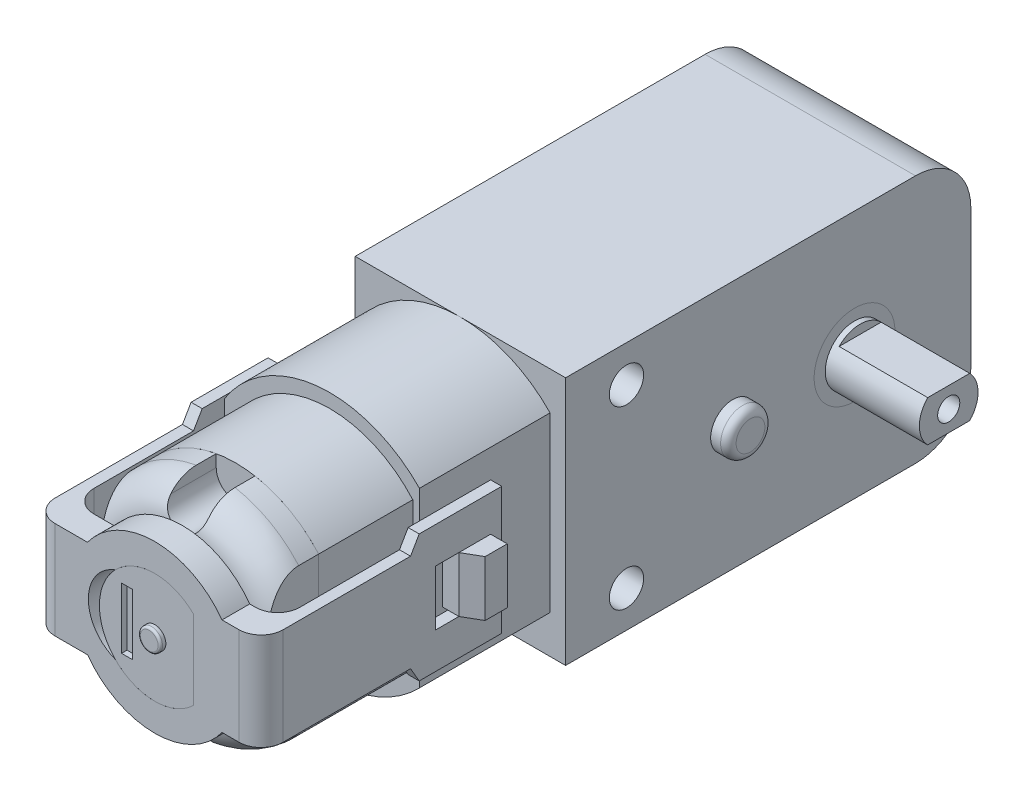
SolidWorks part; units mm, degrees
ref_plane "Alzado" through (0, 0, 0) normal (0, 0, 1) x (1, 0, 0)
ref_plane "Planta" through (0, 0, 0) normal (0, 1, 0) x (1, 0, 0)
ref_plane "Vista lateral" through (0, 0, 0) normal (1, 0, 0) x (0, 0, -1)
sketch "Croquis1" plane through (0, 0, 0) normal (1, 0, 0) x (0, 0, -1)
  line L1 (-18.3, 11.25) -> (13.3, 11.25)
  line L2 (-18.3, 11.25) -> (-18.3, -11.25)
  line L3 (-18.3, -11.25) -> (13.3, -11.25)
  line L4 (18.3, 6.25) -> (18.3, -6.25)
  line L5 (-18.3, 11.25) -> (18.3, -11.25) construction
  line L6 (-18.3, -11.25) -> (18.3, 11.25) construction
  arc A0 (13.3, -11.25) -> (18.3, -6.25) centre (13.3, -6.25) ccw
  arc A1 (13.3, 11.25) -> (18.3, 6.25) centre (13.3, 6.25) cw
  point P0 (0, 0)
  dimension "D3" = 5
  dimension "D1" = 36.6
  dimension "D2" = 22.5
extrude "Saliente-Extruir1" add sketch "Croquis1" along normal mid plane 19
sketch "Croquis2" plane through (9.5, 0, 0) normal (1, 0, 0) x (0, 0, -1)
  line L0 (18.3, 0) -> (-18.3, 0) construction
  line L1 (-18.3, 11.25) -> (-18.3, -11.25) construction
  line L2 (13.3, 11.25) -> (-18.3, 11.25) construction
  circle A0 centre (-12.8, 7.95) radius 1.55
  circle A1 centre (-12.8, -7.95) radius 1.55
  point P6 (0, 0)
  dimension "D1" = 3.1
  dimension "D2" = 3.3
  dimension "D3" = 5.5
extrude "Cortar-Extruir1" cut sketch "Croquis2" against normal through all
sketch "Croquis3" plane through (0, 0, 0) normal (1, 0, 0) x (0, 0, -1)
  line L0 (18.3, -6.25) -> (18.3, 6.25) construction
  line L1 (18.3, 2.5) -> (23.3, 2.5)
  line L2 (18.3, 2.5) -> (18.3, -2.5)
  line L3 (18.3, -2.5) -> (23.3, -2.5)
  line L4 (23.3, 2.5) -> (23.3, -2.5)
  circle A0 centre (20.8, 0) radius 1.55
  point P6 (18.3, 0)
  point P11 (23.3, 0)
  point P13 (20.8, 2.5)
  dimension "D3" = 3.1
  dimension "D1" = 5
  dimension "D2" = 5
extrude "Saliente-Extruir2" add sketch "Croquis3" along normal mid plane 3
sketch "Croquis4" plane through (0, 0, 18.3) normal (0, 0, 1) x (1, 0, 0)
  circle A0 centre (0, 0) radius 11.25
  dimension "D1" = 22.5
extrude "Saliente-Extruir3" add sketch "Croquis4" along normal blind 11.8
sketch "Croquis6" plane through (0, 0, 30.1) normal (0, 0, 1) x (1, 0, 0)
  circle A0 centre (0, 0) radius 10
  dimension "D1" = 20
extrude "Saliente-Extruir4" add sketch "Croquis6" along normal blind 8.5 separate body
sketch "Croquis7" plane through (0, 0, 0) normal (1, 0, 0) x (0, 0, -1)
  line L0 (-38.6, 10) -> (-40.4, 10)
  line L1 (-43.4, 7) -> (-43.4, 5)
  line L3 (-38.6, 10) -> (-38.6, -10) construction
  line L4 (-38.6, 0) -> (-38.6, 10)
  line L5 (18.3, -6.25) -> (18.3, 6.25) construction
  line L6 (-43.4, 5) -> (-45.9, 5)
  line L7 (-45.9, 5) -> (-45.9, 0)
  line L8 (-38.6, 0) -> (-45.9, 0) construction
  line L9 (-38.6, 0) -> (-45.9, 0)
  arc A0 (-40.4, 10) -> (-43.4, 7) centre (-40.4, 7) ccw
  dimension "D1" = 3
  dimension "D2" = 61.7
  dimension "D3" = 2.5
  dimension "D4" = 10
revolve "Revolución1" add sketch "Croquis7" angle 360 about L8
sketch "Croquis8" plane through (0, 0, 30.1) normal (0, 0, 1) x (1, 0, 0)
  line L0 (9.5, -11.25) -> (0, -11.25) construction
  line L1 (-9.5, 11.25) -> (8.1, 11.25)
  line L2 (-9.5, 11.25) -> (-9.5, -11.25)
  line L3 (-9.5, -11.25) -> (8.1, -11.25)
  line L4 (8.1, 11.25) -> (8.1, -11.25)
  line L5 (9.5, -6.026) -> (9.5, -11.25) construction
  line L7 (-13.3448, 14.957) -> (13.3448, 14.957)
  line L8 (-13.3448, 14.957) -> (-13.3448, -14.957)
  line L9 (-13.3448, -14.957) -> (13.3448, -14.957)
  line L10 (13.3448, 14.957) -> (13.3448, -14.957)
  line L11 (-13.3448, 14.957) -> (13.3448, -14.957) construction
  line L12 (-13.3448, -14.957) -> (13.3448, 14.957) construction
  point P9 (0, 0)
  dimension "D1" = 1.4
extrude "Cortar-Extruir2" cut sketch "Croquis8" against normal up to surface (11.8 mm away) up to face at (6.5569, 9.9153, 18.3)
sketch "Croquis9" plane through (0, 0, 45.9) normal (0, 0, 1) x (1, 0, 0)
  line L0 (9.5, -11.25) -> (0, -11.25) construction
  line L1 (-7.5, 11.25) -> (7.5, 11.25)
  line L2 (-7.5, 11.25) -> (-7.5, -11.25)
  line L3 (-7.5, -11.25) -> (7.5, -11.25)
  line L4 (7.5, 11.25) -> (7.5, -11.25)
  line L5 (-7.5, 11.25) -> (7.5, -11.25) construction
  line L6 (-7.5, -11.25) -> (7.5, 11.25) construction
  line L8 (-11.6956, 13.9477) -> (11.6956, 13.9477)
  line L9 (-11.6956, 13.9477) -> (-11.6956, -13.9477)
  line L10 (-11.6956, -13.9477) -> (11.6956, -13.9477)
  line L11 (11.6956, 13.9477) -> (11.6956, -13.9477)
  line L12 (-11.6956, 13.9477) -> (11.6956, -13.9477) construction
  line L13 (-11.6956, -13.9477) -> (11.6956, 13.9477) construction
  point P0 (0, 0)
  point P8 (0, 0)
  dimension "D1" = 15
extrude "Cortar-Extruir3" cut sketch "Croquis9" against normal up to surface (15.8 mm away) up to face at (-0.9164, 0, 30.1)
sketch "Croquis10" plane through (0, 0, 45.9) normal (0, 0, 1) x (1, 0, 0)
  line L1 (3.5, 3.5707) -> (3.5, -3.5707)
  line L2 (-10.6174, 0) -> (10.6174, 0) construction
  circle A1 centre (0, 0) radius 5 construction
  arc A2 (3.5, 3.5707) -> (3.5, -3.5707) centre (0, 0) ccw
  circle A3 centre (0, 0) radius 10.6174
  dimension "D1" = 3.5
extrude "Cortar-Extruir4" cut sketch "Croquis10" against normal up to surface (2.5 mm away) up to face at (0, 5, 43.4)
sketch "Croquis11" plane through (9.5, 0, 0) normal (1, 0, 0) x (0, 0, -1)
  line L0 (18.3, -6.25) -> (18.3, 6.25) construction
  circle A0 centre (7.8, 0) radius 2.65
  circle A1 centre (7.8, 0) radius 3.65
  dimension "D1" = 5.3
  dimension "D3" = 7.3
  dimension "D2" = 10.5
split line "Línea de partición1"
sketch "Croquis12" plane through (9.5, 0, 0) normal (1, 0, 0) x (0, 0, -1)
  circle A1 centre (7.8, 0) radius 2.65
  circle A2 centre (7.8, 0) radius 2.65
  dimension "D1" = 0
extrude "Saliente-Extruir5" add sketch "Croquis12" along normal blind 0.5 separate body
sketch "Croquis13" plane through (10, 0, 0) normal (1, 0, 0) x (0, 0, -1)
  line L0 (5.9026, 1.85) -> (9.6974, 1.85)
  line L1 (5.9026, -1.85) -> (9.6974, -1.85)
  circle A1 centre (7.8, 0) radius 2.65
  circle A2 centre (7.8, 0) radius 2.65
  circle M4 centre (7.8, 0) radius 2.65
  dimension "D2" = 3.7
  dimension "D1" = 0
extrude "Saliente-Extruir6" add sketch "Croquis13" along normal blind 8 contours L1 L0 M4 region at (10, 0, -7.8)
sketch "Croquis14" plane through (18, 0, 0) normal (1, 0, 0) x (0, 0, -1)
  line L0 (5.9026, 1.85) -> (9.6974, 1.85) construction
  circle A0 centre (7.8, 0) radius 1
  arc A1 (9.6974, -1.85) -> (9.6974, 1.85) centre (7.8, 0) ccw construction
  point P5 (7.8, 1.85)
  point P10 (10.45, 0)
  dimension "D1" = 2
extrude "Cortar-Extruir5" cut sketch "Croquis14" against normal blind 8
sketch "Croquis16" plane through (0, 0, 0) normal (0, 1, 0) x (1, 0, 0)
  line L0 (-9.5, -18.3) -> (8.1, -18.3) construction
  line L1 (-0.7, -18.3) -> (-0.7, -30.1) construction
  line L2 (7.5, -30.1) -> (-7.5, -30.1) construction
  line L4 (8.1, -18.3) -> (8.1, -30.1) construction
  line L5 (9.6, -26.5336) -> (9.6, -25.1676)
  line L6 (9.6, -25.1676) -> (11.1, -25.1676)
  line L7 (11.1, -25.1676) -> (11.1, -27.1676)
  line L8 (11.1, -27.1676) -> (8.1, -28.8996)
  line L9 (8.1, -28.8996) -> (8.1, -27.3996)
  line L10 (9.6, -26.5336) -> (8.1, -27.3996)
  line L11 (-11, -26.5336) -> (-9.5, -27.3996)
  line L12 (-9.5, -28.8996) -> (-9.5, -27.3996)
  line L13 (-12.5, -27.1676) -> (-9.5, -28.8996)
  line L14 (-12.5, -25.1676) -> (-12.5, -27.1676)
  line L15 (-11, -25.1676) -> (-12.5, -25.1676)
  line L16 (-11, -26.5336) -> (-11, -25.1676)
  dimension "D1" = 1.5
  dimension "D2" = 60
  dimension "D3" = 10.5996
  dimension "D4" = 1.5
  dimension "D5" = 1.5
  dimension "D6" = 2
extrude "Saliente-Extruir7" add sketch "Croquis16" along normal mid plane 5
sketch "Croquis17" plane through (0, 0, 45.9) normal (0, 0, 1) x (1, 0, 0)
  line L0 (0, 10) -> (0, 8.75) construction
  line L1 (1.75, 10) -> (1.75, 8.75)
  line L2 (-1.75, 10) -> (-1.75, 8.75)
  line L3 (-7, 0) -> (0, 0) construction
  line L4 (0, -10) -> (0, -8.75) construction
  line L5 (1.75, -10) -> (1.75, -8.75)
  line L6 (-1.75, -10) -> (-1.75, -8.75)
  circle A0 centre (0, 0) radius 7 construction
  arc A1 (1.75, 10) -> (-1.75, 10) centre (0, 10) ccw
  arc A2 (-1.75, 8.75) -> (1.75, 8.75) centre (0, 8.75) ccw
  arc A3 (1.75, -10) -> (-1.75, -10) centre (0, -10) cw
  arc A4 (-1.75, -8.75) -> (1.75, -8.75) centre (0, -8.75) cw
  arc A5 (7.5, 6.6144) -> (-7.5, 6.6144) centre (0, 0) ccw construction
  point P6 (0, 9.375)
  point P12 (0, 7)
  point P16 (0, -9.375)
  dimension "D1" = 3
  dimension "D2" = 3.5
extrude "Cortar-Extruir7" cut sketch "Croquis17" against normal up to vertex (7.3 mm away) up to point (7.5, 6.6144, 38.6)
sketch "Croquis18" plane through (9.5, 0, 0) normal (1, 0, 0) x (0, 0, -1)
  circle A0 centre (-3.2, 0) radius 2
  circle A1 centre (7.8, 0) radius 1 construction
  circle A2 centre (7.8, 0) radius 1 construction
  dimension "D2" = 4
  dimension "D1" = 11
extrude "Saliente-Extruir8" add sketch "Croquis18" along normal blind 1.6
fillet "Redondeo1" radius 0.7 1 edges at (11.1, 0, 1.2)
sketch "Croquis19" plane through (0, 0, 45.9) normal (0, 0, 1) x (1, 0, 0)
  line L0 (0, 0) -> (-6, 0) construction
  line L1 (3.5, -3.5707) -> (3.5, 3.5707)
  line L2 (3.5, -3.5707) -> (3.5, 3.5707)
  line L3 (0, 9.3149) -> (0, -9.3149) construction
  line L4 (-6.0737, 4.4) -> (-11, 4.4)
  line L6 (-6.0737, -4.4) -> (-11, -4.4)
  line L7 (-11, 4.4) -> (-11, -4.4)
  line L8 (6.0737, -4.4) -> (9.6, -4.4)
  line L9 (9.6, 4.4) -> (9.6, -4.4)
  line L10 (6.0737, 4.4) -> (9.6, 4.4)
  arc A0 (-3.5707, 3.5) -> (-3.5707, -3.5) centre (-2.264, 0) ccw
  arc A1 (3.5, 3.5707) -> (3.5, -3.5707) centre (0, 0) ccw
  arc A2 (3.5, 3.5707) -> (3.5, -3.5707) centre (0, 0) ccw construction
  circle A3 centre (0, 0) radius 7.5 construction
  arc A4 (-3.5707, 3.5) -> (3.5, 3.5707) centre (0, 0) cw
  arc A5 (-3.5707, -3.5) -> (3.5, -3.5707) centre (0, 0) ccw
  arc A9 (6.0737, 4.4) -> (-6.0737, 4.4) centre (0, 0) ccw
  arc A10 (-6.0737, -4.4) -> (6.0737, -4.4) centre (0, 0) ccw
  point P7 (-5, 0)
  point P16 (-11, 0)
  point P19 (0, 0)
  dimension "D4" = 15
  dimension "D2" = 7
  dimension "D3" = 1
  dimension "D5" = 8.8
  dimension "D1" = 0
extrude "Saliente-Extruir9" add sketch "Croquis19" against normal up to surface (2.5 mm away) separate body up to face at (-0.75, 0, 43.4)
sketch "Croquis20" plane through (0, 0, 45.9) normal (0, 0, 1) x (1, 0, 0)
  line L1 (-3, 2.75) -> (-2, 2.75)
  line L2 (-3, 2.75) -> (-3, -2.75)
  line L3 (-3, -2.75) -> (-2, -2.75)
  line L4 (-2, 2.75) -> (-2, -2.75)
  circle A0 centre (0, 0) radius 1
  point P7 (-2, 0)
  dimension "D1" = 2
  dimension "D2" = 1
  dimension "D3" = 5.5
  dimension "D4" = 2
extrude "Cortar-Extruir8" cut sketch "Croquis20" against normal blind 0.5
sketch "Croquis21" plane through (0, 0, 45.4) normal (0, 0, 1) x (1, 0, 0)
  circle A1 centre (0, 0) radius 1
  circle A2 centre (0, 0) radius 1
  dimension "D1" = 0
extrude "Saliente-Extruir10" add sketch "Croquis21" along normal blind 1 separate body
fillet "Redondeo2" radius 0.2 1 edges at (1, 0, 46.4)
sketch "Croquis23" plane through (0, 0, 0) normal (0, 1, 0) x (1, 0, 0)
  line L0 (-11, -43.4) -> (-11, -24.1676)
  line L1 (-11, -24.1676) -> (-10, -24.1676)
  line L2 (-10, -24.1676) -> (-10, -43.4)
  line L3 (-11, -43.4) -> (-6.0737, -43.4) construction
  line L4 (-10, -43.4) -> (-11, -43.4)
  line L5 (-11, -25.1676) -> (-12.5, -25.1676) construction
  line L6 (9.6, -43.4) -> (9.6, -24.1676)
  line L7 (9.6, -24.1676) -> (8.6, -24.1676)
  line L8 (8.6, -24.1676) -> (8.6, -43.4)
  line L9 (6.0737, -43.4) -> (9.6, -43.4) construction
  line L10 (8.6, -43.4) -> (9.6, -43.4)
  dimension "D1" = 1
  dimension "D2" = 1
extrude "Saliente-Extruir11" add sketch "Croquis23" along normal mid plane 11.5 separate body
combine bodies "Combinar1" operation type add bodies to combine 122 119 123
fillet "Redondeo3" radius 2 4 edges at (-10, 0, 43.4) (9.6, 0, 45.9) (8.6, 0, 43.4) (-11, 0, 45.9)
sketch "Croquis24" plane through (9.6, 0, 0) normal (1, 0, 0) x (0, 0, -1)
  line L0 (-43.4, 4.4) -> (-32.4, 4.4)
  line L1 (-32.4, 4.4) -> (-31.6206, 5.75)
  line L2 (-43.4, 5.75) -> (-24.1676, 5.75) construction
  line L3 (-31.6206, 5.75) -> (-24.6707, 5.75)
  line L4 (-24.6707, 5.75) -> (-24.1676, 0)
  line L5 (-24.1676, 5.75) -> (-24.1676, -5.75) construction
  line L6 (-43.9, 0) -> (-24.1676, 0) construction
  line L7 (-43.9, 4.4) -> (-43.9, -4.4) construction
  line L8 (-43.4, 4.4) -> (-43.358, 0)
  line L9 (-28.0336, 2.5) -> (-30.1676, 2.5)
  line L10 (-28.8996, 2.5) -> (-27.1676, 2.5) construction
  line L11 (-30.1676, 2.5) -> (-30.1676, -2.5)
  line L12 (-27.1676, 2.5) -> (-27.1676, -2.5) construction
  line L13 (-28.0336, 2.5) -> (-28.0336, -2.5)
  line L14 (-28.0336, -2.5) -> (-30.1676, -2.5)
  line L15 (-43.4, -4.4) -> (-43.358, 0)
  line L16 (-24.6707, -5.75) -> (-24.1676, 0)
  line L17 (-31.6206, -5.75) -> (-24.6707, -5.75)
  line L18 (-32.4, -4.4) -> (-31.6206, -5.75)
  line L19 (-43.4, -4.4) -> (-32.4, -4.4)
  line L21 (-49.7676, 7.8072) -> (-18.3, 7.8072)
  line L22 (-49.7676, 7.8072) -> (-49.7676, -7.8072)
  line L23 (-49.7676, -7.8072) -> (-18.3, -7.8072)
  line L24 (-18.3, 7.8072) -> (-18.3, -7.8072)
  line L25 (-49.7676, 7.8072) -> (-18.3, -7.8072) construction
  line L26 (-49.7676, -7.8072) -> (-18.3, 7.8072) construction
  spline S0 degree 3 poles (-40.4, -6.6144) (-40.566, -6.6144) (-40.735, -6.5929) (-41.058, -6.5105) (-41.2143, -6.4497) (-41.5119, -6.2938) (-41.6502, -6.2007) (-41.9086, -5.9885) (-42.0283, -5.8694) (-42.2443, -5.6173) (-42.3419, -5.4832) (-42.5195, -5.2016) (-42.5997, -5.0535) (-42.8128, -4.6025) (-42.9208, -4.2901) (-43.0916, -3.6494) (-43.1542, -3.3204) (-43.2475, -2.6639) (-43.2789, -2.3345) (-43.3461, -1.3445) (-43.3578, -0.6821) (-43.3582, 0.3126) (-43.3548, 0.6482) (-43.3382, 1.3149) (-43.325, 1.648) (-43.2586, 2.6462) (-43.1798, 3.3125) (-42.9257, 4.2747) (-42.817, 4.5922) (-42.6031, 5.0471) (-42.5238, 5.1941) (-42.3463, 5.4768) (-42.2473, 5.6135) (-42.0292, 5.8686) (-41.911, 5.9862) (-41.6535, 6.1982) (-41.5124, 6.2935) (-41.2159, 6.4489) (-41.0605, 6.5098) (-40.7331, 6.5934) (-40.5667, 6.6144) (-40.4, 6.6144) knots 0 0 0 0 0.03125 0.03125 0.0625 0.0625 0.09375 0.09375 0.125 0.125 0.15625 0.15625 0.1875 0.1875 0.25 0.25 0.3125 0.3125 0.375 0.375 0.5 0.5 0.5625 0.5625 0.625 0.625 0.75 0.75 0.8125 0.8125 0.84375 0.84375 0.875 0.875 0.90625 0.90625 0.9375 0.9375 0.96875 0.96875 1 1 1 1 construction
  point P24 (-28.0336, 0)
  point P26 (-30.1676, 0)
  point P30 (-34.0338, 0)
  line M17 (-43.4, 4.4) -> (-43.9, 4.4)
  line M18 (-43.9, 4.4) -> (-43.9, -4.4)
  line M19 (-43.9, -4.4) -> (-43.4, -4.4)
  line M20 (-43.4, -4.4) -> (-43.4, -5.75)
  line M21 (-43.4, -5.75) -> (-24.1676, -5.75)
  line M22 (-24.1676, -5.75) -> (-24.1676, 5.75)
  line M23 (-24.1676, 5.75) -> (-43.4, 5.75)
  line M24 (-43.4, 5.75) -> (-43.4, 4.4)
  dimension "D1" = 5
  dimension "D2" = 30
  dimension "D3" = 11
  dimension "D4" = 3
extrude "Cortar-Extruir9" cut sketch "Croquis24" against normal up to surface (1.5 mm away) contours L24 L21 L22 L23 M17 M24 M23 M22 M21 M20 M19 M18 | L14 L13 L9 L11 | L19 L18 M20 M21 | L15 L8 M19 M17 M18 | L0 L1 M23 M24 region at (9.6, 5.0827, 37.7029) region at (9.6, 0, 43.6394) region at (9.6, -5.0827, 37.7029) region at (9.6, 0, 29.1006) region at (9.6, 7.4559, 34.0338) up to face at (8.1, 0, 24.2)
sketch "Croquis26" plane through (-11, 0, 0) normal (-1, 0, 0) x (0, 0, 1)
  line L0 (28.0336, 2.5) -> (30.1676, 2.5) construction
  line L1 (30.1676, 2.5) -> (30.1676, -2.5) construction
  line L2 (28.0336, -2.5) -> (30.1676, -2.5) construction
  line L3 (28.0336, 2.5) -> (28.0336, -2.5) construction
  line L4 (31.6206, -5.75) -> (24.6707, -5.75) construction
  line L5 (24.6707, -5.75) -> (24.1676, 0) construction
  line L6 (24.6707, 5.75) -> (24.1676, 0) construction
  line L7 (31.6206, 5.75) -> (24.6707, 5.75) construction
  line L8 (32.4, 4.4) -> (31.6206, 5.75) construction
  line L9 (43.4, 4.4) -> (32.4, 4.4) construction
  line L10 (43.4, 4.4) -> (43.358, 0) construction
  line L11 (43.4, -4.4) -> (43.358, 0) construction
  line L12 (43.4, -4.4) -> (32.4, -4.4) construction
  line L13 (32.4, -4.4) -> (31.6206, -5.75) construction
  line L14 (28.0336, 2.5) -> (30.1676, 2.5)
  line L15 (30.1676, 2.5) -> (30.1676, -2.5)
  line L16 (28.0336, -2.5) -> (30.1676, -2.5)
  line L17 (28.0336, 2.5) -> (28.0336, -2.5)
  line L18 (31.6206, -5.75) -> (24.6707, -5.75)
  line L19 (24.6707, -5.75) -> (24.1676, 0)
  line L20 (24.6707, 5.75) -> (24.1676, 0)
  line L21 (31.6206, 5.75) -> (24.6707, 5.75)
  line L22 (32.4, 4.4) -> (31.6206, 5.75)
  line L23 (43.4, 4.4) -> (32.4, 4.4)
  line L24 (43.4, 4.4) -> (43.358, 0)
  line L25 (43.4, -4.4) -> (43.358, 0)
  line L26 (43.4, -4.4) -> (32.4, -4.4)
  line L27 (32.4, -4.4) -> (31.6206, -5.75)
  line L28 (49.7676, 7.8072) -> (49.7676, -7.8072) construction
  line L29 (49.7676, 7.8072) -> (18.3, 7.8072) construction
  line L30 (18.3, 7.8072) -> (18.3, -7.8072) construction
  line L31 (49.7676, -7.8072) -> (18.3, -7.8072) construction
  line L32 (49.7676, 7.8072) -> (18.3, -7.8072) construction
  line L33 (43.9, 0) -> (24.1676, 0) construction
  line L34 (49.7676, -7.8072) -> (18.3, 7.8072) construction
  line L35 (49.7676, 7.8072) -> (49.7676, -7.8072)
  line L36 (49.7676, 7.8072) -> (18.3, 7.8072)
  line L37 (18.3, 7.8072) -> (18.3, -7.8072)
  line L38 (49.7676, -7.8072) -> (18.3, -7.8072)
  line L39 (49.7676, 7.8072) -> (18.3, -7.8072) construction
  line L40 (43.9, 0) -> (24.1676, 0) construction
  line L41 (49.7676, -7.8072) -> (18.3, 7.8072) construction
  line M12 (43.4, -4.4) -> (43.9, -4.4)
  line M13 (43.9, -4.4) -> (43.9, 4.4)
  line M14 (43.9, 4.4) -> (43.4, 4.4)
  line M15 (43.4, 4.4) -> (43.4, 5.75)
  line M16 (43.4, 5.75) -> (24.1676, 5.75)
  line M17 (24.1676, 5.75) -> (24.1676, -5.75)
  line M18 (24.1676, -5.75) -> (43.4, -5.75)
  line M19 (43.4, -5.75) -> (43.4, -4.4)
extrude "Cortar-Extruir12" cut sketch "Croquis26" against normal up to surface (1.5 mm away) contours L38 L35 L36 L37 M12 M19 M18 M17 M16 M15 M14 M13 | L23 L22 M15 M16 | L26 L27 M18 M19 | L19 M18 M17 | L20 M16 M17 | L14 L17 L16 L15 region at (-11, 0, 29.1006) region at (-11, -5.0827, 37.7029) region at (-11, -3.8333, 24.3353) region at (-11, 3.8333, 24.3353) region at (-11, 5.0827, 37.7029) region at (-11, 0, 49.4163) up to face at (-9.5, 0, 28.1496)
other "Eliminar cara1" face at (8.1, 0, 44.3662) face at (8.85, 2.2, 43.379) face at (8.85, -2.2, 43.379) and patch yes
other "Eliminar cara2" face at (-10.25, 0, 43.9) face at (-9.5, 0, 44.8682) and patch yes
